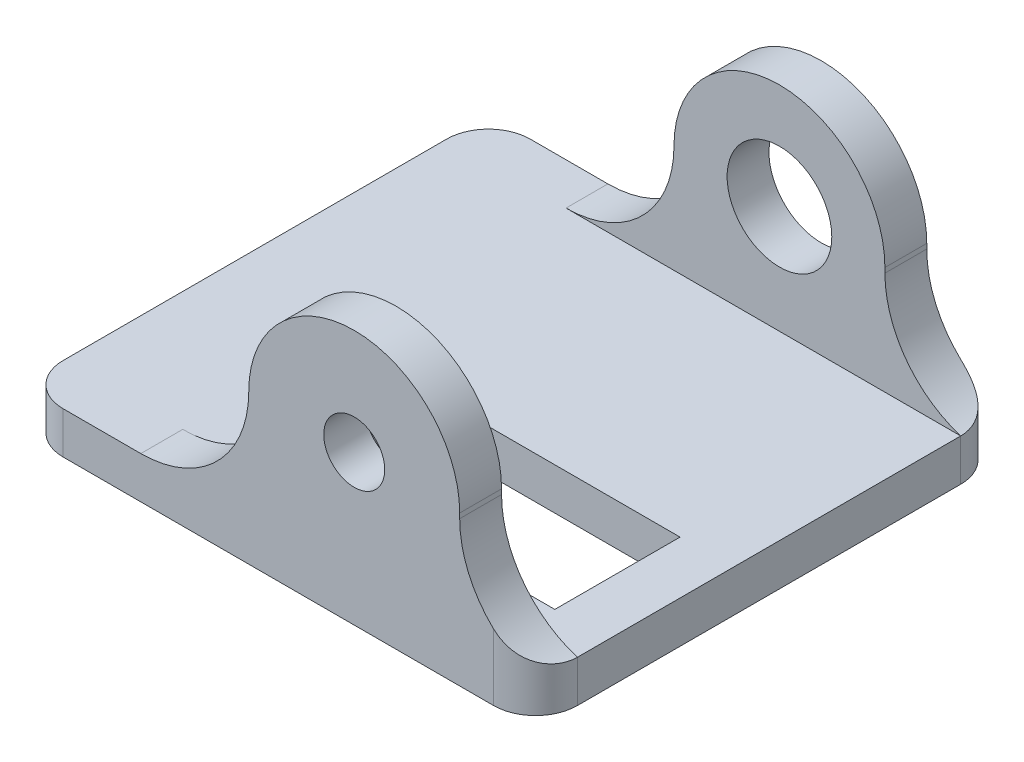
SolidWorks part; units mm, degrees
material "ABS PC"
ref_plane "Front Plane" through (0, 0, 0) normal (0, 0, 1) x (1, 0, 0)
ref_plane "Top Plane" through (0, 0, 0) normal (0, 1, 0) x (1, 0, 0)
ref_plane "Right Plane" through (0, 0, 0) normal (1, 0, 0) x (0, 0, -1)
sketch "Sketch1" plane through (0, 0, 0) normal (0, 1, 0) x (1, 0, 0)
  line L1 (-27.5, -20.43) -> (27.5, -20.43)
  line L2 (-27.5, -20.43) -> (-27.5, 50.43)
  line L3 (-27.5, 50.43) -> (27.5, 50.43)
  line L4 (27.5, -20.43) -> (27.5, 50.43)
  line L7 (-19.5, -9.5) -> (19.5, -9.5)
  line L8 (-19.5, -9.5) -> (-19.5, 9.5)
  line L9 (-19.5, 9.5) -> (19.5, 9.5)
  line L10 (19.5, -9.5) -> (19.5, 9.5)
  line L11 (-19.5, -9.5) -> (19.5, 9.5) construction
  line L12 (-19.5, 9.5) -> (19.5, -9.5) construction
  point P0 (0, 0)
  point P6 (0, 0)
  dimension "D1" = 40.93
  dimension "D2" = 55
  dimension "D3" = 19
  dimension "D4" = 39
  dimension "D5" = 8
  dimension "D6" = 8
  dimension "D7" = 10.93
extrude "Boss-Extrude1" add sketch "Sketch1" along normal blind 6.35
sketch "Sketch12" plane through (0, 0, -50.43) normal (0, 0, 1) x (1, 0, 0)
  line L4 (0, 6.35) -> (0, 22.7287) construction
  line L10 (27.5, 6.35) -> (-27.5, 6.35) construction
  line L12 (0, 22.7287) -> (16, 22.7287) construction
  line L13 (16, 22.7287) -> (16, 6.35)
  line L15 (0, 22.7287) -> (-16, 22.7287) construction
  line L16 (-16, 22.7287) -> (-16, 6.35)
  line L17 (-16, 6.35) -> (16, 6.35)
  circle A2 centre (0, 22.7287) radius 7.94
  arc A4 (16, 22.7287) -> (-16, 22.7287) centre (0, 22.7287) ccw
  dimension "D1" = 15.88
  dimension "D2" = 16
extrude "Boss-Extrude11" add sketch "Sketch12" along normal blind 6.35
sketch "Sketch16" plane through (0, 0, 20.43) normal (0, 0, 1) x (1, 0, 0)
  line L0 (-16, 6.35) -> (-16, 22.7287)
  line L1 (16, 6.35) -> (16, 22.7287)
  line L2 (16, 6.35) -> (-16, 6.35)
  arc A0 (-16, 22.7287) -> (16, 22.7287) centre (0, 22.7287) cw
extrude "Boss-Extrude14" add sketch "Sketch16" against normal blind 6.35
sketch "Sketch15" plane through (0, 6.35, 0) normal (0, 1, 0) x (1, 0, 0)
  line L0 (-27.5, 50.43) -> (-50.5, 50.43)
  line L1 (-27.5, -20.43) -> (-50.5, -20.43)
  line L2 (-50.5, -20.43) -> (-50.5, 50.43)
  line L3 (-27.5, 50.43) -> (-27.5, -20.43)
  line L4 (-16, 50.43) -> (-27.5, 50.43) construction
  point P2 (0, 0)
  point P7 (0, 0)
  dimension "D1" = 23
extrude "Boss-Extrude13" add sketch "Sketch15" against normal up to surface (6.35 mm away) from surface at 0 up to face at (0, 0, -15) starting at face at (0, 6.35, -15)
fillet "Fillet2" radius 16.38 4 edges at (16, 6.35, -47.255) (16, 6.35, 17.255) (-16, 6.35, 17.255) (-16, 6.35, -47.255)
fillet "Fillet3" radius 6.35 4 edges at (27.5, 3.175, -50.43) (27.5, 3.175, 20.43) (-50.5, 3.175, 20.43) (-50.5, 3.175, -50.43)
sketch "Sketch17" plane through (0, 0, 14.08) normal (0, 0, -1) x (-1, 0, 0)
  circle A0 centre (0, 22.7287) radius 4.625
  dimension "D1" = 9.25
extrude "Cut-Extrude1" cut sketch "Sketch17" against normal up to next
